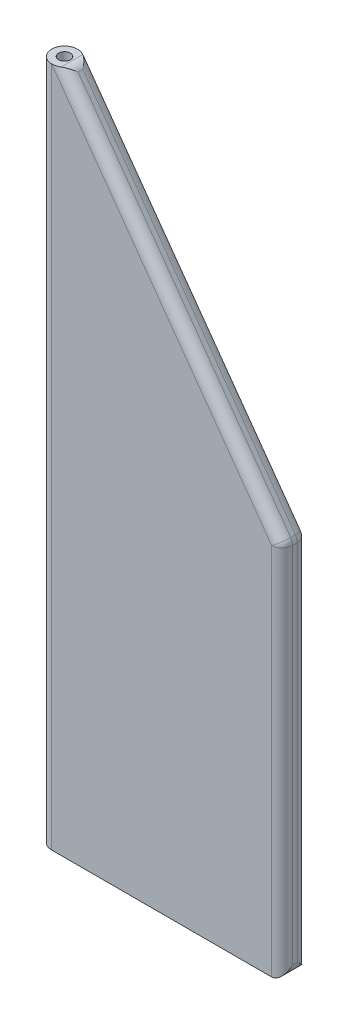
SolidWorks part; units mm, degrees
ref_plane "Front" through (0, 0, 0) normal (0, 0, 1) x (1, 0, 0)
ref_plane "Top" through (0, 0, 0) normal (0, 1, 0) x (1, 0, 0)
ref_plane "Right" through (0, 0, 0) normal (1, 0, 0) x (0, 0, -1)
sketch "Sketch1" plane through (0, 0, 0) normal (0, 1, 0) x (1, 0, 0)
  line L0 (0, 1.225) -> (22, 1.225)
  line L1 (22, 1.225) -> (22, -1.225)
  line L2 (22, -1.225) -> (0, -1.225)
  circle A0 centre (0, 0) radius 0.425 construction
  circle A1 centre (0, 0) radius 1.225
  circle A2 centre (0, 0) radius 0.56
  dimension "D1" = 0.85
  dimension "D2" = 0.8
  dimension "D3" = 22
  dimension "D4" = 0.135
extrude "Boss-Extrude1" add sketch "Sketch1" along normal blind 65 contours A1 A0 region at (0.8417, 0, -0.8417)
extrude "Boss-Extrude2" add sketch "Sketch1<4>" along normal blind 36 contours A1 L2 L1 L0 region at (11.4793, 0, 0)
sketch "Sketch1<4>" plane through (0, 0, 0) normal (0, 1, 0) x (1, 0, 0) same geometry as "Sketch1"
sketch "Sketch2" plane through (0, 0, 0) normal (0, 0, 1) x (1, 0, 0)
  line L0 (1.225, 65) -> (22, 36)
  line L1 (1.225, 65) -> (-1.225, 65) construction
  line L2 (1.225, 36) -> (1.225, 65) construction
  line L3 (22, 36) -> (0, 36)
  line L4 (0, 36) -> (0, 65)
  line L5 (0, 65) -> (1.225, 65)
extrude "Boss-Extrude3" add sketch "Sketch2" along normal up to surface and the other way up to surface up to face at (11, 18, 1.225) other way up to face at (11, 18, -1.225)
sketch "Sketch3" plane through (0, 0, 0) normal (0, 1, 0) x (1, 0, 0)
  circle A4 centre (0, 0) radius 0.56 construction
  circle A7 centre (0, 0) radius 0.56
extrude "Cut-Extrude1" cut sketch "Sketch3" along normal through all both and the other way through all
fillet "Fillet2" radius 1 7 edges at (22, 18, 1.225) (22, 18, -1.225) (22, 0, 0) (1.225, 65, 0) (11.6125, 50.5, -1.225) (22, 36, 0) (11.6125, 50.5, 1.225)
equation "\"D3@Sketch1\"=4.4m /200"
equation "\"D1@Boss-Extrude1\"= 7.2m / 200"
equation "\"D1@Boss-Extrude2\"=7.2m /200"
